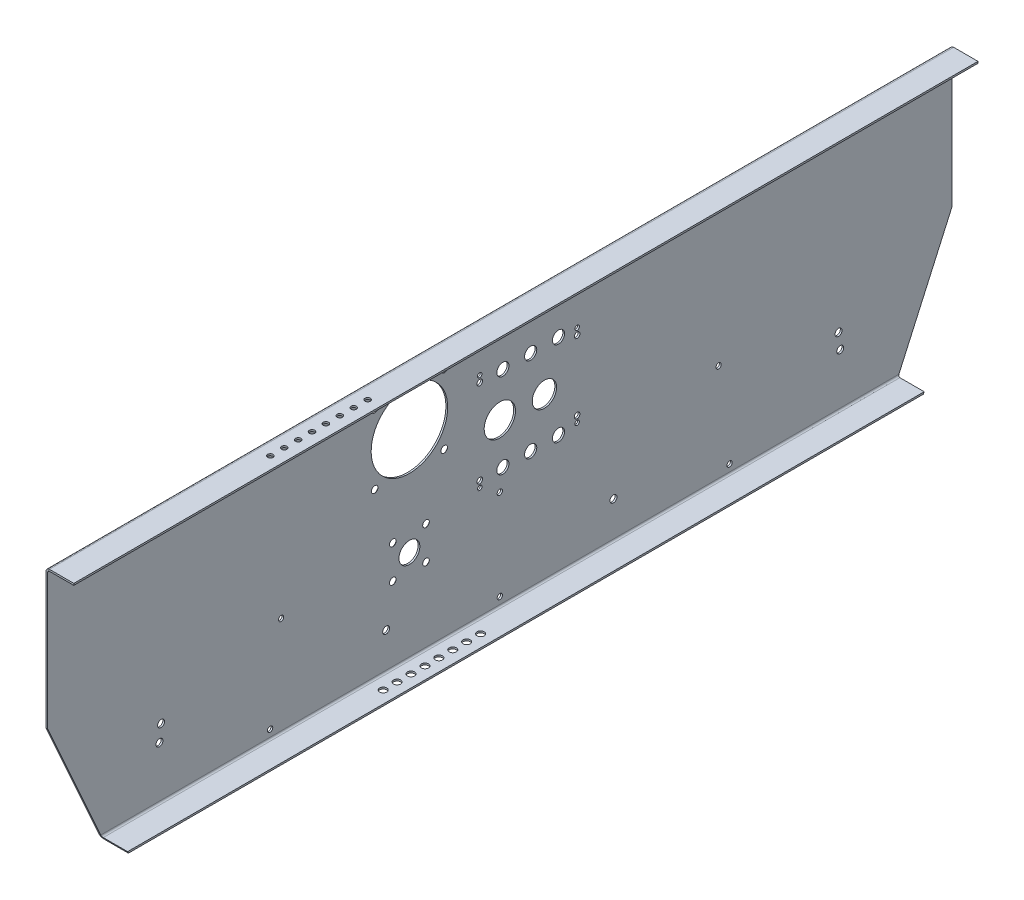
SolidWorks part; units mm, degrees
material "6061-T6 (SS)"
ref_plane "Front Plane" through (0, 0, 0) normal (0, 0, 1) x (1, 0, 0)
ref_plane "Top Plane" through (0, 0, 0) normal (0, 1, 0) x (1, 0, 0)
ref_plane "Right Plane" through (0, 0, 0) normal (1, 0, 0) x (0, 0, -1)
sketch "Sketch3" plane through (0, 0, 0) normal (0, 0, 1) x (1, 0, 0)
  line L0 (3.175, 233.4895) -> (25.4, 233.4895)
  line L1 (0, 231.902) -> (0, 0)
  line L4 (1.5875, 0) -> (1.5875, 231.902)
  line L5 (25.4, 233.4895) -> (25.4, 235.077)
  line L6 (25.4, 235.077) -> (3.175, 235.077)
  line L7 (0, 115.951) -> (26.891, 115.951) construction
  line L8 (25.4, -1.5875) -> (25.4, -3.175)
  line L9 (3.175, -1.5875) -> (25.4, -1.5875)
  line L10 (25.4, -3.175) -> (3.175, -3.175)
  arc A0 (0, 231.902) -> (3.175, 235.077) centre (3.175, 231.902) cw
  arc A1 (1.5875, 231.902) -> (3.175, 233.4895) centre (3.175, 231.902) cw
  arc A2 (0, 0) -> (3.175, -3.175) centre (3.175, 0) ccw
  arc A3 (1.5875, 0) -> (3.175, -1.5875) centre (3.175, 0) ccw
  dimension "D3" = 1.5875
  dimension "D4" = 1.5875
  dimension "D1" = 1.5875
  dimension "D2" = 231.902
  dimension "D5" = 25.4
base flange "Base-Flange2" sketch "Sketch3" thickness 825.5 reverse thickness direction no parameters "D1"=0.7366
sketch "Sketch1" plane through (0, 0, 0) normal (1, 0, 0) x (0, 0, -1)
  line L0 (0, 0) -> (825.5, 0) construction
  line L1 (407.3648, 6.35) -> (418.1352, 6.35) construction
  line L2 (825.5, 0) -> (825.5, 95.25) construction
  line L3 (0, 95.25) -> (825.5, 95.25) construction
  line L4 (0, 95.25) -> (0, 0) construction
  line L5 (622.4782, 0) -> (622.4782, 6.35) construction
  line L6 (-12.1207, 0) -> (-42.1566, 0) construction
  line L7 (-44.9273, -69.85) -> (939.266, -69.85) construction
  line L8 (825.5, -69.85) -> (825.5, 107.95) construction
  line L9 (308.991, 31.75) -> (516.509, 31.75) construction
  line L10 (151.2485, 31.75) -> (358.7665, 31.75) construction
  line L11 (516.509, 31.75) -> (722.0074, 60.6309) construction
  line L12 (308.991, 31.75) -> (103.4926, 60.6309) construction
  line L13 (412.75, 0) -> (412.75, 6.35) construction
  line L14 (412.75, 95.25) -> (412.75, 88.9) construction
  line L15 (612.4655, 95.25) -> (612.4655, 88.9) construction
  line L16 (614.8828, 6.35) -> (630.0737, 6.35) construction
  line L17 (600.5116, 88.9) -> (624.4194, 88.9) construction
  line L18 (203.0218, 0) -> (203.0218, 6.35) construction
  line L19 (195.4263, 6.35) -> (210.6172, 6.35) construction
  line L20 (213.0345, 95.25) -> (213.0345, 88.9) construction
  line L21 (308.991, 31.75) -> (101.9785, 46.2257) construction
  line L22 (516.509, 31.75) -> (723.5215, 46.2257) construction
  line L23 (201.0806, 88.9) -> (224.9884, 88.9) construction
  line L24 (1.8926, 60.6309) -> (386.0676, 60.6309) construction
  line L25 (453.4662, 146.002) -> (412.75, 146.002) construction
  line L26 (394.4379, 190.579) -> (394.4379, 184.737) construction
  line L27 (394.4379, 107.267) -> (394.4379, 101.425) construction
  line L28 (412.75, 146.002) -> (394.4379, 107.267) construction
  line L29 (412.75, 146.002) -> (394.4379, 184.737) construction
  line L30 (412.75, 146.002) -> (415.5199, 184.737) construction
  line L31 (412.75, 146.002) -> (415.5199, 107.267) construction
  line L32 (453.4662, 146.002) -> (440.9199, 107.267) construction
  line L33 (453.4662, 146.002) -> (466.3199, 107.267) construction
  line L34 (453.4662, 146.002) -> (466.3199, 184.737) construction
  line L35 (453.4662, 146.002) -> (440.9199, 184.737) construction
  line L36 (453.4662, 146.002) -> (483.3379, 177.752) construction
  line L37 (483.3379, 183.594) -> (483.3379, 177.752) construction
  line L38 (453.4662, 146.002) -> (483.3379, 114.252) construction
  line L39 (483.3379, 114.252) -> (483.3379, 108.41) construction
  line L40 (386.0676, 0) -> (386.0676, 95.25) construction
  line L41 (412.75, 146.002) -> (516.509, 31.75) construction
  line L42 (412.75, 146.002) -> (308.991, 31.75) construction
  line L43 (825.5, 231.902) -> (825.5, 0) construction
  line L44 (825.5, -3.175) -> (0, -3.175) construction
  line L45 (330.2, 82.55) -> (330.2, 179.9336) construction
  line L46 (825.5, -3.175) -> (775.673, -3.175)
  line L47 (775.673, -3.175) -> (825.5, 107.95)
  line L48 (825.5, 107.95) -> (825.5, -3.175)
  line L49 (0, 107.95) -> (0, -3.175)
  line L50 (49.827, -3.175) -> (0, 107.95)
  line L51 (0, -3.175) -> (49.827, -3.175)
  line L52 (0, 231.902) -> (0, 0) construction
  line L53 (345.3575, 67.3926) -> (315.0425, 67.3925) construction
  line L54 (345.3575, 67.3926) -> (345.3575, 97.7074) construction
  line L55 (345.3575, 97.7074) -> (315.0425, 97.7074) construction
  line L56 (315.0425, 67.3925) -> (315.0425, 97.7074) construction
  line L57 (345.3575, 67.3926) -> (315.0425, 97.7074) construction
  line L58 (345.3575, 97.7074) -> (315.0425, 67.3925) construction
  line L59 (361.95, 148.1836) -> (298.45, 148.1836) construction
  line L60 (361.95, 148.1836) -> (361.95, 211.6836) construction
  line L61 (361.95, 211.6836) -> (298.45, 211.6836) construction
  line L62 (298.45, 148.1836) -> (298.45, 211.6836) construction
  line L63 (361.95, 148.1836) -> (298.45, 211.6836) construction
  line L64 (361.95, 211.6836) -> (298.45, 148.1836) construction
  circle A0 centre (516.509, 31.75) radius 3.175
  circle A1 centre (308.991, 31.75) radius 3.175
  circle A2 centre (308.991, 31.75) radius 101.6 construction
  circle A3 centre (516.509, 31.75) radius 101.6 construction
  circle A4 centre (103.4926, 60.6309) radius 3.175
  circle A5 centre (722.0074, 60.6309) radius 3.175
  circle A6 centre (722.0074, 60.6309) radius 101.6 construction
  circle A7 centre (103.4926, 60.6309) radius 101.6 construction
  circle A8 centre (412.75, 6.35) radius 2.413
  circle A9 centre (412.75, 88.9) radius 2.413
  circle A10 centre (622.4782, 6.35) radius 2.413
  circle A11 centre (612.4655, 88.9) radius 2.413
  circle A12 centre (203.0218, 6.35) radius 2.413
  circle A13 centre (101.9785, 46.2257) radius 3.175
  circle A14 centre (101.9785, 46.2257) radius 101.6 construction
  circle A15 centre (723.5215, 46.2257) radius 3.175
  circle A16 centre (723.5215, 46.2257) radius 101.6 construction
  circle A17 centre (213.0345, 88.9) radius 2.413
  circle A18 centre (213.0345, 88.9) radius 4.7625 construction
  circle A19 centre (722.0074, 60.6309) radius 50.4825 construction
  circle A20 centre (516.509, 31.75) radius 50.4825 construction
  circle A21 centre (308.991, 31.75) radius 50.4825 construction
  circle A22 centre (103.4926, 60.6309) radius 50.4825 construction
  circle A23 centre (453.4662, 146.002) radius 30.48 construction
  circle A24 centre (466.3199, 184.737) radius 5.5562
  circle A25 centre (483.3379, 177.752) radius 2.5527
  circle A26 centre (483.3379, 183.594) radius 2.0447
  circle A27 centre (483.3379, 114.252) radius 2.5527
  circle A28 centre (483.3379, 108.41) radius 2.0447
  circle A29 centre (466.3199, 107.267) radius 5.5562
  circle A30 centre (440.9199, 107.267) radius 5.5562
  circle A31 centre (415.5199, 107.267) radius 5.5563
  circle A32 centre (394.4379, 107.267) radius 2.5527
  circle A33 centre (394.4379, 101.425) radius 2.0447
  circle A34 centre (394.4379, 184.737) radius 2.5527
  circle A35 centre (394.4379, 190.579) radius 2.0447
  circle A36 centre (412.75, 146.002) radius 14.2812
  circle A37 centre (453.4662, 146.002) radius 11.1061
  circle A38 centre (440.9199, 184.737) radius 5.5562
  circle A39 centre (415.5199, 184.737) radius 5.5562
  circle A40 centre (345.3575, 97.7074) radius 1.5875
  circle A41 centre (315.0425, 97.7074) radius 1.5875
  circle A42 centre (315.0425, 67.3925) radius 1.5875
  circle A43 centre (345.3575, 67.3926) radius 1.5875
  circle A44 centre (330.2, 82.55) radius 9.525
  circle A45 centre (361.95, 211.6836) radius 1.27
  circle A46 centre (298.45, 211.6836) radius 1.27
  circle A47 centre (298.45, 148.1836) radius 1.27
  circle A48 centre (361.95, 148.1836) radius 1.27
  circle A49 centre (330.2, 179.9336) radius 34.925
  circle A50 centre (330.2, 82.55) radius 36.5 construction
  circle A51 centre (330.2, 179.9336) radius 30 construction
  point P16 (419.9974, 0)
  point P17 (412.75, 31.75)
  point P18 (419.9974, 0)
  point P21 (412.75, 31.75)
  point P32 (516.509, 28.575)
  point P33 (516.509, 34.925)
  point P34 (722.0074, 63.8059)
  point P35 (722.0074, 57.4559)
  point P36 (405.5026, 0)
  point P43 (388.3025, 95.25)
  point P44 (437.1975, 95.25)
  point P114 (801.073, -3.175)
  point P115 (775.673, -3.175)
  point P124 (330.2, 82.55)
  point P137 (330.2, 179.9336)
  dimension "D3" = 207.518
  dimension "D5" = 203.2
  dimension "D4" = 6.35
  dimension "D10" = 63.5
  dimension "D15" = 4.826
  dimension "D18" = 6.35
  dimension "D21" = 4
  dimension "D22" = 101.9785
  dimension "D23" = 9.525
  dimension "D24" = 100.965
  dimension "D26" = 60.96
  dimension "D42" = 22.2123
  dimension "D43" = 11.1125
  dimension "D44" = 40.7162
  dimension "D47" = 5.1054
  dimension "D48" = 4.0894
  dimension "D50" = 28.5623
  dimension "D51" = 30.3149
  dimension "D55" = 330.2
  dimension "D56" = 85.725
  dimension "D57" = 3.175
  dimension "D58" = 19.05
  dimension "D60" = 2.54
  dimension "D61" = 69.85
  dimension "D62" = 73
  dimension "D63" = 60
  dimension "D2" = 6.35
  dimension "D6" = 8
  dimension "D7" = 8
  dimension "D8" = 154.3355
  dimension "D9" = 31.75
  dimension "D11" = 177.8
  dimension "D12" = 6.35
  dimension "D13" = 25.4
  dimension "D14" = 6.35
  dimension "D16" = 6.35
  dimension "D17" = 6.35
  dimension "D19" = 48.8951
  dimension "D20" = 4
  dimension "D25" = 384.175
  dimension "D27" = 43.5934
  dimension "D28" = 46.746
  dimension "D29" = 5.842
  dimension "D30" = 136.746
  dimension "D31" = 46.746
  dimension "D32" = 24.896
  dimension "D33" = 36.305
  dimension "D34" = 36.305
  dimension "D35" = 24.896
  dimension "D36" = 40.812
  dimension "D37" = 85.91
  dimension "D38" = 85.91
  dimension "D39" = 29.393
  dimension "D40" = 29.393
  dimension "D41" = 40.7162
  dimension "D45" = 38.8339
  dimension "D46" = 42.8454
  dimension "D49" = 5.842
  dimension "D52" = 154.697
  dimension "D53" = 154.697
  dimension "D54" = 136.746
  dimension "D59" = 63.5
  dimension "D64" = 97.3836
  dimension "D65" = 330.2
sketch "Bend-Lines3" plane through (0, 0, 0) normal (0, 1, 0) x (1, 0, 0)
sketch "Bounding-Box3" plane through (0, 0, 0) normal (0, 1, 0) x (1, 0, 0)
extrude "Cut-Extrude3" cut sketch "Sketch1" along normal through all normal cut yes
hole_wizard "CSK for #10 Flat Head Machine Screw (100)1" positions "Sketch7" profile "Sketch6" countersink size "#10" standard "ANSI Inch" end condition through all
sketch "Sketch7" plane through (0, 0, 0) normal (-1, 0, 0) x (0, 0, 1)
  point P0 (-345.3575, 97.7074)
  point P3 (-315.0425, 97.7074)
  point P6 (-315.0425, 67.3925)
  point P9 (-345.3575, 67.3926)
  point P12 (-298.45, 148.1836)
  point P15 (-361.95, 148.1836)
  point P18 (-361.95, 211.6836)
  point P21 (-298.45, 211.6836)
sketch "Sketch6" plane through (0, 97.7074, -345.3575) normal (0, 1, 0) x (0, 0, 1)
  line L0 (0, 0) -> (0, 25.4)
  line L1 (0, 25.4) -> (2.4892, 25.4)
  line L2 (2.4892, 25.4) -> (2.4892, 2.0141)
  line L3 (2.4892, 2.0141) -> (4.8895, 0)
  line L5 (4.8895, 0) -> (0, 0)
  line L6 (-2.4892, 2.0141) -> (-4.8895, 0) construction
  line L11 (0, -6.35) -> (0, 107.95) construction
  dimension "Thru Hole Dia." = 4.9784
  dimension "Thru Hole Depth" = 25.4
  dimension "Near C'Sink Dia." = 9.779
  dimension "Near C'Sink Angle" = 100
sketch "Sketch8" plane through (0, -1.5875, 0) normal (0, 1, 0) x (1, 0, 0)
  line L1 (3.175, 407.881) -> (25.4, 407.881) construction
  line L2 (3.175, 776.3848) -> (3.175, 49.1152) construction
  line L3 (25.4, 776.3848) -> (25.4, 49.1152) construction
  line L4 (3.175, 49.1152) -> (25.4, 49.1152) construction
  line L5 (14.2875, 407.881) -> (14.2875, 382.481) construction
  circle A0 centre (14.2875, 382.481) radius 0.635
  circle A1 centre (14.2875, 369.781) radius 0.635
  circle A2 centre (14.2875, 357.081) radius 0.635
  circle A3 centre (14.2875, 344.381) radius 0.635
  circle A4 centre (14.2875, 331.681) radius 0.635
  circle A5 centre (14.2875, 318.981) radius 0.635
  circle A6 centre (14.2875, 306.281) radius 0.635
  circle A7 centre (14.2875, 293.581) radius 0.635
  dimension "D2" = 25.4
  dimension "D3" = 1.27
  dimension "D1" = 358.7658
  dimension "D4" = 8
extrude "Cut-Extrude4" cut sketch "Sketch8" against normal through all normal cut yes
hole_wizard "1/4 Clearance Hole1" positions "Sketch13" profile "Sketch11" hole size "1/4" standard "ANSI Inch" end condition through all
sketch "Sketch13" plane through (0, -1.5875, 0) normal (0, 1, 0) x (1, 0, 0)
  point P0 (14.2875, 382.481)
  point P3 (14.2875, 369.781)
  point P6 (14.2875, 357.081)
  point P9 (14.2875, 344.381)
  point P12 (14.2875, 331.681)
  point P15 (14.2875, 318.981)
  point P18 (14.2875, 306.281)
  point P21 (14.2875, 293.581)
  point P24 (14.2875, 331.681)
  point P30 (14.2875, 318.981)
sketch "Sketch11" plane through (14.2875, -1.5875, -382.481) normal (1, 0, 0) x (0, 0, 1)
  line L0 (0, 0) -> (0, 1.5875)
  line L1 (0, 1.5875) -> (3.2639, 1.5875)
  line L2 (3.2639, 1.5875) -> (3.2639, 0)
  line L5 (3.2639, 0) -> (0, 0)
  line L11 (0, -6.35) -> (0, 107.95) construction
  dimension "Thru Hole Dia." = 6.5278
  dimension "Thru Hole Depth" = 1.5875
sketch "Sketch14" plane through (0, 233.4895, 0) normal (0, -1, 0) x (1, 0, 0)
  line L0 (3.175, -279.4) -> (25.4, -279.4) construction
  line L1 (3.175, -825.5) -> (3.175, 0) construction
  line L2 (25.4, -825.5) -> (25.4, 0) construction
  line L3 (3.175, 0) -> (25.4, 0) construction
  circle A0 centre (14.2875, -279.4) radius 0.635
  circle A1 centre (14.2875, -266.7) radius 0.635
  circle A2 centre (14.2875, -254) radius 0.635
  circle A3 centre (14.2875, -241.3) radius 0.635
  circle A4 centre (14.2875, -228.6) radius 0.635
  circle A5 centre (14.2875, -215.9) radius 0.635
  circle A6 centre (14.2875, -203.2) radius 0.635
  circle A7 centre (14.2875, -190.5) radius 0.635
  dimension "D2" = 1.27
  dimension "D1" = 279.4
  dimension "D3" = 8
hole_wizard "#8 Clearance Hole1" positions "Sketch16" profile "Sketch15" hole size "#8" standard "ANSI Inch" end condition through all
sketch "Sketch16" plane through (0, 233.4895, 0) normal (0, -1, 0) x (-1, 0, 0)
  point P0 (-14.2875, 279.4)
  point P3 (-14.2875, 266.7)
  point P6 (-14.2875, 254)
  point P9 (-14.2875, 241.3)
  point P12 (-14.2875, 228.6)
  point P15 (-14.2875, 215.9)
  point P18 (-14.2875, 203.2)
  point P21 (-14.2875, 190.5)
sketch "Sketch15" plane through (14.2875, 233.4895, -279.4) normal (1, 0, 0) x (0, 0, -1)
  line L0 (0, 0) -> (0, 1.5875)
  line L1 (0, 1.5875) -> (2.4574, 1.5875)
  line L2 (2.4574, 1.5875) -> (2.4574, 0)
  line L5 (2.4574, 0) -> (0, 0)
  line L11 (0, -6.35) -> (0, 107.95) construction
  dimension "Thru Hole Dia." = 4.9149
  dimension "Thru Hole Depth" = 1.5875
sheet metal parameters "Sheet-Metal3" thickness 825.5 parameters "D1"=0.7366, "D7"=685.8
flat pattern "Flat-Pattern3"
sketch "Bend-Lines4" plane through (0, 0, 0) normal (0, 1, 0) x (1, 0, 0)
sketch3d "Bounding-Box4"
  line L0 (22.2247, -3.175, 0) -> (22.225, 235.077, 0) construction
  line L1 (-3.175, -3.175, 0) -> (-3.1747, 235.077, 0) construction
  line L2 (22.2247, -3.175, 0) -> (-3.175, -3.175, 0) construction
  line L3 (22.225, 235.077, 0) -> (-3.1747, 235.077, 0) construction
